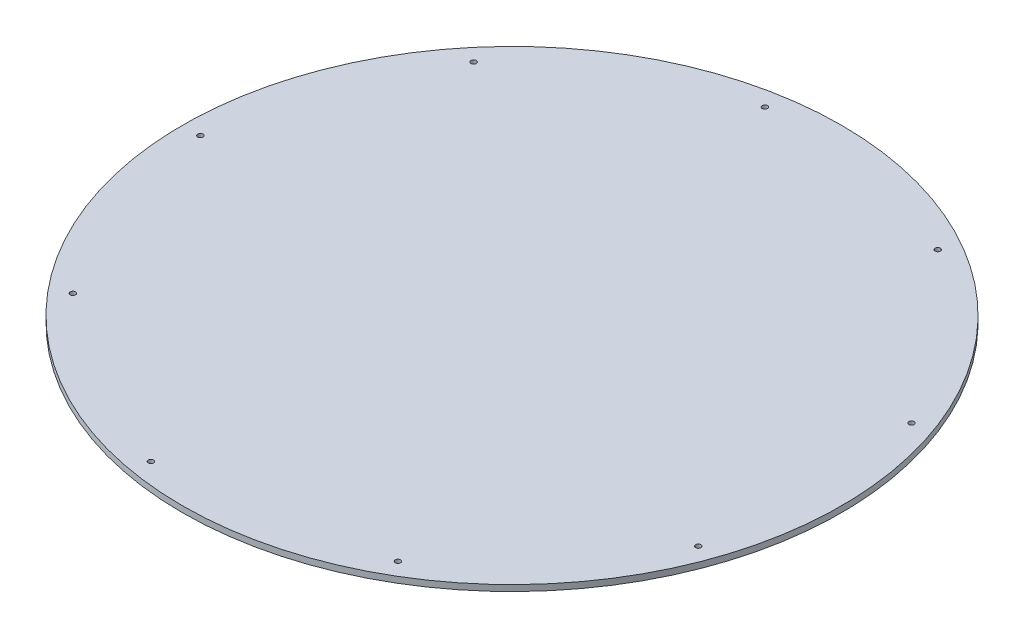
SolidWorks part; units mm, degrees
ref_plane "Front Plane" through (0, 0, 0) normal (0, 0, 1) x (1, 0, 0)
ref_plane "Top Plane" through (0, 0, 0) normal (0, 1, 0) x (1, 0, 0)
ref_plane "Right Plane" through (0, 0, 0) normal (1, 0, 0) x (0, 0, -1)
sketch "Sketch1" plane through (0, 0, 0) normal (0, 1, 0) x (1, 0, 0)
  circle A0 centre (0, 0) radius 318.262
  dimension "D1" = 636.524
extrude "Boss-Extrude1" add sketch "Sketch1" along normal blind 5.842
ref_axis "Axis1" through (0, 6.6675, 0) along (0, -1, 0)
sketch "Sketch2" plane through (0, 5.842, 0) normal (0, 1, 0) x (1, 0, 0)
  line L0 (0, 0) -> (-300.99, 0) construction
  circle A0 centre (-300.99, 0) radius 2.5527
  dimension "D2" = 5.1054
  dimension "D1" = 300.99
extrude "Cut-Extrude1" cut sketch "Sketch2" against normal through all
pattern_circular "CirPattern1" count 9 over 360 about axis through (0, 6.6675, 0) along (0, -1, 0) of "Cut-Extrude1"
